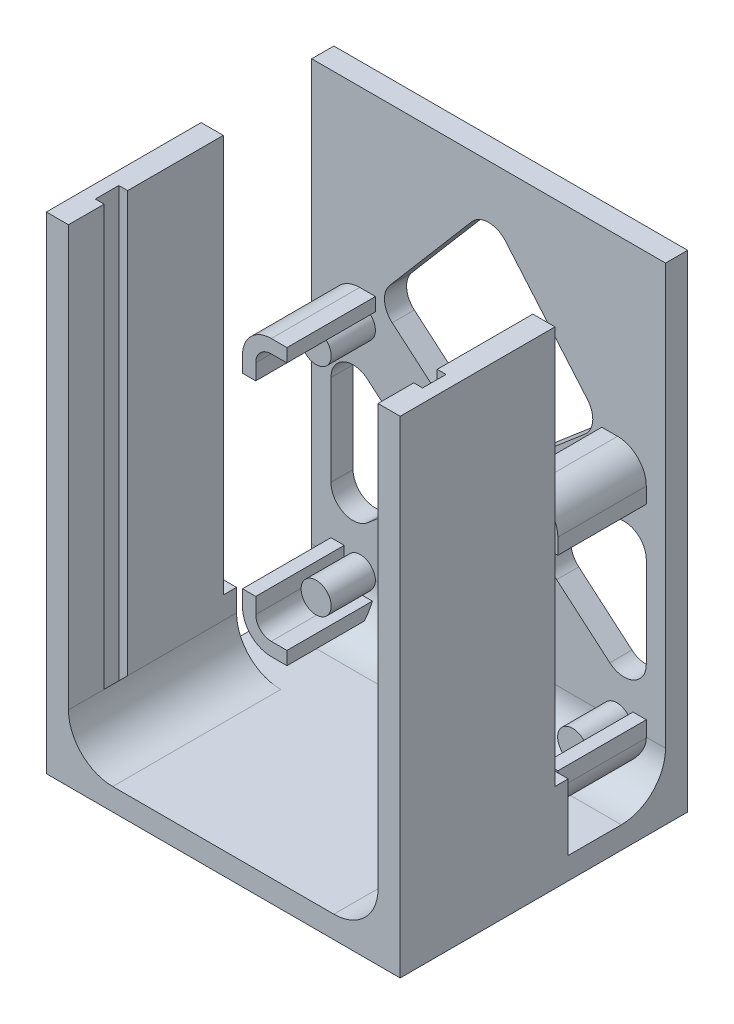
SolidWorks part; units mm, degrees
note: The reader was unsure of these and kept them because the rebuilt part matched: shared geometry of "Sketch1<3>", "Sketch1<4>".
ref_plane "Front" through (0, 0, 0) normal (0, 0, 1) x (1, 0, 0)
ref_plane "Top" through (0, 0, 0) normal (0, 1, 0) x (1, 0, 0)
ref_plane "Right" through (0, 0, 0) normal (1, 0, 0) x (0, 0, -1)
sketch "Sketch1" plane through (0, 0, 0) normal (0, 0, 1) x (1, 0, 0)
  line L0 (-29.15, 15.65) -> (29.15, 15.65)
  line L1 (-40, -55) -> (40, -55)
  line L2 (-40, -55) -> (-40, 55)
  line L3 (-40, 55) -> (40, 55)
  line L4 (40, -55) -> (40, 55)
  line L5 (-40, -55) -> (40, 55) construction
  line L6 (-40, 55) -> (40, -55) construction
  line L7 (-29, -40) -> (29, -40) construction
  line L8 (-29, -40) -> (-29, 9) construction
  line L9 (-29, 9) -> (29, 9) construction
  line L10 (29, -40) -> (29, 9) construction
  line L11 (-29, -40) -> (29, 9) construction
  line L12 (-29, 9) -> (29, -40) construction
  line L13 (-29.15, -43.65) -> (-25.6, -43.65)
  line L14 (-32.65, -40.15) -> (-32.65, -36.6)
  line L15 (-29.15, 12.65) -> (-25.6, 12.65)
  line L16 (32.65, -40.15) -> (32.65, -36.6)
  line L17 (-32.65, -43.65) -> (32.65, 12.65) construction
  line L18 (-32.65, 12.65) -> (32.65, -43.65) construction
  line L19 (35.65, -40.15) -> (35.65, 9.15)
  line L20 (-29.15, -46.65) -> (29.15, -46.65)
  line L21 (-35.65, -40.15) -> (-35.65, 9.15)
  line L22 (-29, 5.6) -> (-35.65, 5.6)
  line L23 (-25.6, 9) -> (-25.6, 15.65)
  line L24 (25.6, 9) -> (25.6, 15.65)
  line L25 (29, 5.6) -> (35.65, 5.6)
  line L26 (29, -36.6) -> (35.65, -36.6)
  line L27 (25.6, -40) -> (25.6, -46.65)
  line L28 (-29, -36.6) -> (-35.65, -36.6)
  line L29 (-25.6, -40) -> (-25.6, -46.65)
  line L30 (-32.65, 5.6) -> (-32.65, 9.15)
  line L31 (25.6, -43.65) -> (29.15, -43.65)
  line L32 (-32.65, -36.6) -> (-32.65, 5.6) construction
  line L33 (-32.65, -40.15) -> (-32.65, 9.15) construction
  line L34 (32.65, 5.6) -> (32.65, 9.15)
  line L35 (-25.6, -43.65) -> (25.6, -43.65) construction
  line L36 (-29.15, -43.65) -> (29.15, -43.65) construction
  line L37 (25.6, 12.65) -> (29.15, 12.65)
  line L38 (32.65, -36.6) -> (32.65, 5.6) construction
  line L39 (32.65, -40.15) -> (32.65, 9.15) construction
  line L41 (-25.6, 12.65) -> (25.6, 12.65) construction
  line L42 (-29.15, 12.65) -> (29.15, 12.65) construction
  circle A0 centre (-29, 9) radius 3.4
  circle A1 centre (29, 9) radius 3.4
  circle A2 centre (29, -40) radius 3.4
  circle A3 centre (-29, -40) radius 3.4
  arc A4 (-29.15, -43.65) -> (-32.65, -40.15) centre (-29.15, -40.15) cw
  arc A5 (29.15, -43.65) -> (32.65, -40.15) centre (29.15, -40.15) ccw
  arc A6 (29.15, 12.65) -> (32.65, 9.15) centre (29.15, 9.15) cw
  arc A7 (-32.65, 9.15) -> (-29.15, 12.65) centre (-29.15, 9.15) cw
  arc A8 (29.15, 15.65) -> (35.65, 9.15) centre (29.15, 9.15) cw
  arc A9 (29.15, -46.65) -> (35.65, -40.15) centre (29.15, -40.15) ccw
  arc A10 (-29.15, -46.65) -> (-35.65, -40.15) centre (-29.15, -40.15) cw
  arc A11 (-35.65, 9.15) -> (-29.15, 15.65) centre (-29.15, 9.15) cw
  point P0 (0, 0)
  point P10 (0, -15.5)
  point P15 (0, -15.5)
  dimension "D6" = 6.8
  dimension "D9" = 3.5
  dimension "D1" = 80
  dimension "D2" = 110
  dimension "D3" = 58
  dimension "D4" = 49
  dimension "D5" = 30
  dimension "D7" = 56.3
  dimension "D8" = 65.3
  dimension "D10" = 3
extrude "Boss-Extrude1" add sketch "Sketch1" along normal blind 5
extrude "Boss-Extrude3" add sketch "Sketch1<3>" along normal blind 15 contours A0 | A1 | A2 | A3
sketch "Sketch1<3>" plane through (0, 0, 0) normal (0, 0, 1) x (1, 0, 0) same geometry as "Sketch1"
extrude "Boss-Extrude4" add sketch "Sketch1<4>" along normal blind 25 contours A11 L21 L22 L30 A7 L15 L23 L0 | A8 L0 L24 L37 A6 L34 L25 L19 | L20 A9 L19 L26 L16 A5 L31 L27 | A10 L20 L29 L13 A4 L14 L28 L21
sketch "Sketch1<4>" plane through (0, 0, 0) normal (0, 0, 1) x (1, 0, 0) same geometry as "Sketch1"
sketch "Sketch2" plane through (0, 0, 5) normal (0, 0, 1) x (1, 0, 0)
  line L0 (40, -55) -> (40, 55) construction
  line L1 (-40, -55) -> (40, -55)
  line L2 (-40, -55) -> (-40, -50)
  line L3 (-40, -50) -> (40, -50)
  line L4 (40, -55) -> (40, -50)
  dimension "D1" = 5
extrude "Boss-Extrude5" add sketch "Sketch2" along normal blind 60
sketch "Sketch3" plane through (0, -50, 0) normal (0, 1, 0) x (1, 0, 0)
  line L0 (-35.65, -25) -> (-35.65, -5) construction
  line L1 (-40, -65) -> (-35, -65)
  line L2 (-40, -65) -> (-40, -27)
  line L3 (-40, -27) -> (-35, -27)
  line L4 (-35, -65) -> (-35, -27)
  line L5 (-35.65, -25) -> (-35.65, -5)
  line L6 (0, -50) -> (0, 50) construction
  line L7 (40, -27) -> (35, -27)
  line L8 (35, -65) -> (35, -27)
  line L9 (40, -65) -> (35, -65)
  line L10 (40, -65) -> (40, -27)
  line M6 (-40, -5) -> (-40, -65)
  line M7 (-40, -65) -> (40, -65)
  line M8 (40, -65) -> (40, -5)
  dimension "D1" = 5
  dimension "D2" = 2
extrude "Boss-Extrude6" add sketch "Sketch3" along normal blind 15 contours L4 L3 M7 M6 | L8 L7 M7 M8
sketch "Sketch4" plane through (0, -35, 0) normal (0, 1, 0) x (1, 0, 0)
  line L0 (35, -27) -> (35, -65) construction
  line L1 (35, -65) -> (40, -65) construction
  line L2 (40, -65) -> (40, -27) construction
  line L3 (40, -27) -> (35, -27) construction
  line L4 (-40, -65) -> (-35, -65) construction
  line L5 (-35, -65) -> (-35, -27) construction
  line L6 (-35, -27) -> (-40, -27) construction
  line L7 (-40, -27) -> (-40, -65) construction
  line L8 (35, -27) -> (35, -65)
  line L9 (35, -65) -> (40, -65)
  line L10 (40, -65) -> (40, -27)
  line L11 (40, -27) -> (35, -27)
  line L12 (-40, -65) -> (-35, -65)
  line L13 (-35, -65) -> (-35, -27)
  line L14 (-35, -27) -> (-40, -27)
  line L15 (-40, -27) -> (-40, -65)
  line L16 (-40, -30) -> (-35, -30)
  line L18 (35, -30) -> (40, -30)
  line M8 (-40, -65) -> (-35, -65)
  line M9 (-35, -65) -> (-35, -27)
  dimension "D1" = 35
extrude "Boss-Extrude7" add sketch "Sketch4" along normal up to surface (90 mm away) contours L16 L15 M8 M9 | L18 L8 L9 L10 up to face at (0, 55, 2.5)
fillet "Fillet1" radius 10 3 edges at (-35, -50, 46) (35, -50, 46) (0, -50, 5)
sketch "Sketch5" plane through (0, 55, 0) normal (0, 1, 0) x (1, 0, 0)
  line L0 (-35, -65) -> (-35, -30) construction
  line L1 (-35, -65) -> (-35, -30)
  line L2 (37, -51.625) -> (-37, -51.625)
  line L3 (-37, -51.625) -> (-37, -56.925)
  line L4 (36.85, -51.775) -> (-36.85, -51.775)
  line L5 (-36.85, -51.775) -> (-36.85, -56.775)
  line L6 (-36.85, -56.775) -> (36.85, -56.775)
  line L7 (36.85, -56.775) -> (36.85, -51.775)
  line L8 (36.85, -51.775) -> (-36.85, -51.775) construction
  line L9 (-36.85, -51.775) -> (-36.85, -56.775) construction
  line L10 (-36.85, -56.775) -> (36.85, -56.775) construction
  line L11 (36.85, -56.775) -> (36.85, -51.775) construction
  line L12 (-37, -56.925) -> (37, -56.925)
  line L13 (37, -56.925) -> (37, -51.625)
  line L14 (35, -30) -> (35, -65) construction
  line L15 (35, -30) -> (35, -65)
  dimension "D2" = 0.15
  dimension "D1" = 0
extrude "Cut-Extrude1" cut sketch "Sketch5" against normal up to surface (105 mm away) contours L3 L12 L1 L2 | L2 L15 L12 L13
sketch "Sketch6" plane through (0, 0, 5) normal (0, 0, 1) x (1, 0, 0)
  line L2 (25.6, -46.65) -> (29.15, -46.65) construction
  line L3 (35.65, -40.15) -> (35.65, -36.6) construction
  line L4 (35.65, -36.6) -> (32.65, -36.6) construction
  line L5 (32.65, -36.6) -> (32.65, -40.15) construction
  line L6 (29.15, -43.65) -> (25.6, -43.65) construction
  line L7 (25.6, -43.65) -> (25.6, -46.65) construction
  line L8 (-29.15, -46.65) -> (-25.6, -46.65) construction
  line L9 (-25.6, -46.65) -> (-25.6, -43.65) construction
  line L10 (-25.6, -43.65) -> (-29.15, -43.65) construction
  line L11 (-32.65, -40.15) -> (-32.65, -36.6) construction
  line L12 (-32.65, -36.6) -> (-35.65, -36.6) construction
  line L13 (-35.65, -36.6) -> (-35.65, -40.15) construction
  line L14 (-35.65, 9.15) -> (-35.65, 5.6) construction
  line L15 (-35.65, 5.6) -> (-32.65, 5.6) construction
  line L16 (-32.65, 5.6) -> (-32.65, 9.15) construction
  line L17 (-29.15, 12.65) -> (-25.6, 12.65) construction
  line L18 (-25.6, 12.65) -> (-25.6, 15.65) construction
  line L19 (-25.6, 15.65) -> (-29.15, 15.65) construction
  line L20 (29.15, 15.65) -> (25.6, 15.65) construction
  line L21 (25.6, 15.65) -> (25.6, 12.65) construction
  line L22 (25.6, 12.65) -> (29.15, 12.65) construction
  line L23 (32.65, 9.15) -> (32.65, 5.6) construction
  line L24 (32.65, 5.6) -> (35.65, 5.6) construction
  line L25 (35.65, 5.6) -> (35.65, 9.15) construction
  line L26 (25.6, -46.65) -> (29.15, -46.65)
  line L27 (35.65, -40.15) -> (35.65, -36.6)
  line L28 (35.65, -36.6) -> (32.65, -36.6)
  line L29 (32.65, -36.6) -> (32.65, -40.15)
  line L30 (29.15, -43.65) -> (25.6, -43.65)
  line L31 (25.6, -43.65) -> (25.6, -46.65)
  line L32 (-29.15, -46.65) -> (-25.6, -46.65)
  line L33 (-25.6, -46.65) -> (-25.6, -43.65)
  line L34 (-25.6, -43.65) -> (-29.15, -43.65)
  line L35 (-32.65, -40.15) -> (-32.65, -36.6)
  line L36 (-32.65, -36.6) -> (-35.65, -36.6)
  line L37 (-35.65, -36.6) -> (-35.65, -40.15)
  line L38 (-35.65, 9.15) -> (-35.65, 5.6)
  line L39 (-35.65, 5.6) -> (-32.65, 5.6)
  line L40 (-32.65, 5.6) -> (-32.65, 9.15)
  line L41 (-29.15, 12.65) -> (-25.6, 12.65)
  line L42 (-25.6, 12.65) -> (-25.6, 15.65)
  line L43 (-25.6, 15.65) -> (-29.15, 15.65)
  line L44 (29.15, 15.65) -> (25.6, 15.65)
  line L45 (25.6, 15.65) -> (25.6, 12.65)
  line L46 (25.6, 12.65) -> (29.15, 12.65)
  line L47 (32.65, 9.15) -> (32.65, 5.6)
  line L48 (32.65, 5.6) -> (35.65, 5.6)
  line L49 (35.65, 5.6) -> (35.65, 9.15)
  line L50 (-35.65, -36.6) -> (25.6, 15.65)
  line L51 (35.65, 5.6) -> (-25.6, -46.65)
  line L52 (35.65, -36.6) -> (-25.6, 15.65)
  line L53 (-35.65, 5.6) -> (25.6, -46.65)
  line L54 (35.65, 5.6) -> (35.65, -36.6)
  line L55 (25.6, 15.65) -> (-25.6, 15.65)
  line L56 (-35.65, 5.6) -> (-35.65, -36.6)
  line L57 (-25.6, -46.65) -> (25.6, -46.65)
  line L58 (-25.6, 15.65) -> (0, 45.6596)
  line L59 (0, 45.6596) -> (25.6, 15.65)
  arc A1 (29.15, -46.65) -> (35.65, -40.15) centre (29.15, -40.15) ccw construction
  arc A2 (29.15, -43.65) -> (32.65, -40.15) centre (29.15, -40.15) ccw construction
  arc A3 (-35.65, -40.15) -> (-29.15, -46.65) centre (-29.15, -40.15) ccw construction
  arc A4 (-32.65, -40.15) -> (-29.15, -43.65) centre (-29.15, -40.15) ccw construction
  arc A5 (-29.15, 15.65) -> (-35.65, 9.15) centre (-29.15, 9.15) ccw construction
  arc A6 (-29.15, 12.65) -> (-32.65, 9.15) centre (-29.15, 9.15) ccw construction
  arc A7 (35.65, 9.15) -> (29.15, 15.65) centre (29.15, 9.15) ccw construction
  arc A8 (32.65, 9.15) -> (29.15, 12.65) centre (29.15, 9.15) ccw construction
  arc A9 (29.15, -46.65) -> (35.65, -40.15) centre (29.15, -40.15) ccw
  arc A10 (29.15, -43.65) -> (32.65, -40.15) centre (29.15, -40.15) ccw
  arc A11 (-35.65, -40.15) -> (-29.15, -46.65) centre (-29.15, -40.15) ccw
  arc A12 (-32.65, -40.15) -> (-29.15, -43.65) centre (-29.15, -40.15) ccw
  arc A13 (-29.15, 15.65) -> (-35.65, 9.15) centre (-29.15, 9.15) ccw
  arc A14 (-29.15, 12.65) -> (-32.65, 9.15) centre (-29.15, 9.15) ccw
  arc A15 (35.65, 9.15) -> (29.15, 15.65) centre (29.15, 9.15) ccw
  arc A16 (32.65, 9.15) -> (29.15, 12.65) centre (29.15, 9.15) ccw
  line M11 (-25.6, -40) -> (25.6, -40)
extrude "Cut-Extrude2" cut sketch "Sketch6" against normal up to next contours L59 L58 L55 | L50 L55 L52 | L53 L56 L50 | L53 L51 M11 | L54 L51 L52
fillet "Fillet2" radius 5 13 edges at (-17.8045, -40, 2.5) (0, -24.8116, 2.5) (17.8045, -40, 2.5) (-10.9156, -15.5, 2.5) (-35.65, 5.6, 2.5) (-35.65, -36.6, 2.5) (35.65, -36.6, 2.5) (35.65, 5.6, 2.5) (10.9156, -15.5, 2.5) (0, -6.1884, 2.5) (-25.6, 15.65, 2.5) (25.6, 15.65, 2.5) (0, 45.6596, 2.5)
